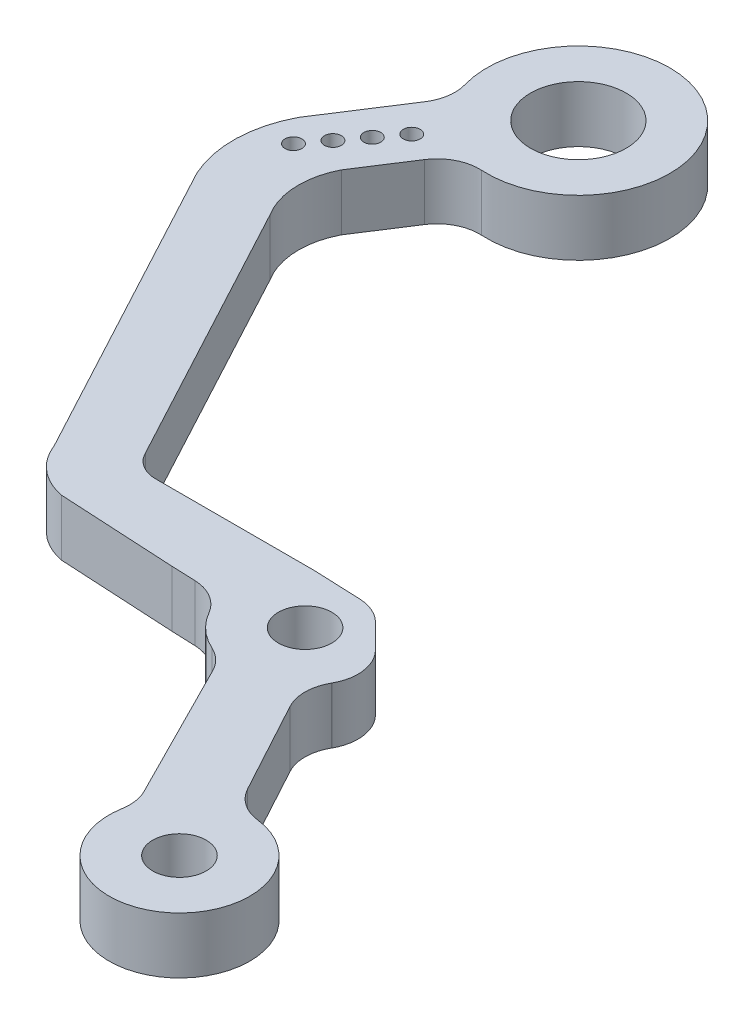
SolidWorks part; units mm, degrees
ref_plane "Front Plane" through (0, 0, 0) normal (0, 0, 1) x (1, 0, 0)
ref_plane "Top Plane" through (0, 0, 0) normal (0, 1, 0) x (1, 0, 0)
ref_plane "Right Plane" through (0, 0, 0) normal (1, 0, 0) x (0, 0, -1)
sketch "Sketch1" plane through (0, 0, 0) normal (0, 1, 0) x (1, 0, 0)
  line L0 (143.3333, 493) -> (716.6667, 493) construction
sketch "Sketch2" plane through (0, 0, 0) normal (0, 1, 0) x (1, 0, 0)
  line L0 (45.2788, 103.9326) -> (40.9177, 97.1844)
  line L1 (51.9956, 69.1217) -> (40.7298, 90.14)
  line L2 (58.0479, 69.8647) -> (65.4047, 69.8647)
  line L3 (64.0439, 65.0687) -> (56.5756, 65.4741)
  line L4 (49.0625, 100.7287) -> (45.662, 95.4669)
  line L5 (45.9135, 90.14) -> (56.2122, 70.926)
  line L6 (45.9135, 90.14) -> (45.5308, 90.8539)
  line L7 (65.4047, 69.8647) -> (69.3416, 69.8647)
  line L8 (77.3922, 49.2355) -> (71.3644, 61.1602)
  line L9 (69.3416, 69.8647) -> (73.8824, 69.6766)
  line L10 (73.8824, 69.6766) -> (77.5387, 66.0204)
  line L11 (51.9956, 69.1217) -> (52.4488, 68.2763)
  line L13 (56.9043, 65.4562) -> (55.7376, 65.5195)
  line L14 (81.2785, 52.4716) -> (75.9262, 62.3428)
  line L17 (64.0439, 65.0687) -> (67.6597, 64.927)
  circle A5 centre (72.5387, 66.0204) radius 1.9
  circle A7 centre (82.0956, 47.5388) radius 1.9
  arc A9 (45.662, 95.4669) -> (45.9135, 90.14) centre (50.4346, 93.0228) ccw
  arc A10 (41.6771, 98.3595) -> (40.7298, 90.14) centre (47.9508, 93.4721) ccw
  circle A11 centre (51.0536, 106.9163) radius 3.4
  arc A13 (52.4488, 68.2763) -> (55.7376, 65.5195) centre (56.5568, 69.837) ccw
  arc A14 (56.116, 71.1054) -> (58.0479, 69.8647) centre (58.0835, 72.0445) ccw
  arc A15 (67.6597, 64.927) -> (71.3644, 61.1602) centre (72.5387, 66.0204) ccw
  arc A16 (49.0625, 100.7287) -> (45.2788, 103.9326) centre (51.0536, 106.9163) ccw
  arc A17 (75.9262, 62.3428) -> (77.5387, 66.0204) centre (72.5387, 66.0204) ccw
  arc A19 (77.3922, 49.2355) -> (81.2785, 52.4716) centre (82.0956, 47.5388) ccw
extrude "Boss-Extrude1" add sketch "Sketch2" along normal blind 4 contours L7 L2 A14 L5 A9 L4 L0 A10 L1 L11 A13 L13 L3 L17 L8 A5 A7 A11 region at (54.7041, 0, -111.2273)
sketch "Sketch3" plane through (0, 4, 0) normal (0, 1, 0) x (1, 0, 0)
  circle A0 centre (42.3534, 95.379) radius 0.6
  circle A1 centre (43.5576, 96.9758) radius 0.6
  circle A2 centre (44.7618, 98.5727) radius 0.6
  circle A3 centre (45.9659, 100.1695) radius 0.6
extrude "Cut-Extrude1" cut sketch "Sketch3" against normal blind 6
fillet "Fillet1" radius 3 9 edges at (77.5387, 2, -66.0204) (73.8824, 2, -69.6766) (75.9262, 2, -62.3428) (77.3922, 2, -49.2355) (81.2785, 2, -52.4716) (71.3644, 2, -61.1602) (67.6597, 2, -64.927) (45.2788, 2, -103.9326) (49.0625, 2, -100.7287)
